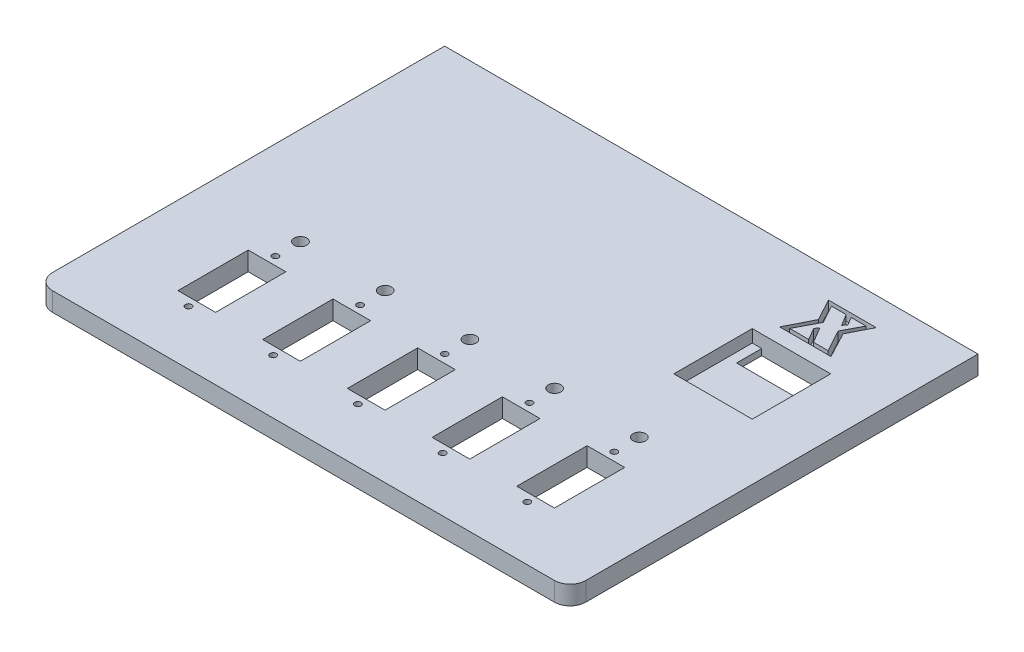
SolidWorks part; units mm, degrees
ref_plane "Front Plane" through (0, 0, 0) normal (0, 0, 1) x (1, 0, 0)
ref_plane "Top Plane" through (0, 0, 0) normal (0, 1, 0) x (1, 0, 0)
ref_plane "Right Plane" through (0, 0, 0) normal (1, 0, 0) x (0, 0, -1)
sketch "Sketch1" plane through (0, 0, 0) normal (0, 1, 0) x (1, 0, 0)
  line L1 (-85, -65) -> (85, -65)
  line L2 (-85, -65) -> (-85, 65)
  line L3 (-85, 65) -> (85, 65)
  line L4 (85, -65) -> (85, 65)
  line L5 (-85, -65) -> (85, 65) construction
  line L6 (-85, 65) -> (85, -65) construction
  point P0 (0, 0)
  dimension "D1" = 170
  dimension "D2" = 130
extrude "Boss-Extrude1" add sketch "Sketch1" along normal blind 6
sketch "Sketch2" plane through (0, 6, 0) normal (0, 1, 0) x (1, 0, 0)
  line L0 (-85, 65) -> (-85, -65) construction
  line L1 (-60, -45) -> (-48, -45)
  line L2 (-60, -45) -> (-60, -22.6)
  line L3 (-60, -22.6) -> (-48, -22.6)
  line L4 (-48, -45) -> (-48, -22.6)
  line L5 (-60, -45) -> (-48, -22.6) construction
  line L6 (-60, -22.6) -> (-48, -45) construction
  line L7 (-85, -65) -> (85, -65) construction
  circle A0 centre (-54, -19.95) radius 1
  circle A1 centre (-54, -47.65) radius 1
  circle A2 centre (-54, -11.95) radius 2
  point P0 (-54, -51.3962)
  point P14 (-54, -33.8)
  dimension "D5" = 2
  dimension "D6" = 2
  dimension "D12" = 4
  dimension "D13" = 8
  dimension "D14" = 6
  dimension "D15" = 6
  dimension "D1" = 12
  dimension "D2" = 22.4
  dimension "D3" = 25
  dimension "D4" = 20
  dimension "D7" = 27.7
  dimension "D8" = 2.65
  dimension "D9" = 2.65
  dimension "D10" = 13.85
  dimension "D11" = 13.85
extrude "Cut-Extrude1" cut sketch "Sketch2" against normal blind 10
pattern_linear "LPattern1" count 5 spacing 27 along (1, 0, 0) of "Cut-Extrude1"
sketch "Sketch8" plane through (0, 6, 0) normal (0, 1, 0) x (1, 0, 0)
  line L0 (85, 65) -> (-85, 65) construction
  line L1 (67, 11.05) -> (42, 11.05)
  line L2 (67, 11.05) -> (67, 36.05)
  line L3 (67, 36.05) -> (42, 36.05)
  line L4 (42, 11.05) -> (42, 36.05)
  line L6 (85, -65) -> (85, 65) construction
  dimension "D1" = 25
  dimension "D2" = 25
  dimension "D4" = 18
  dimension "D5" = 28.95
extrude "Cut-Extrude5" cut sketch "Sketch8" against normal through all
fillet "Fillet2" radius 5 2 edges at (-85, 3, 65) (85, 3, 65)
sketch "Sketch10" plane through (0, 0, 0) normal (0, -1, 0) x (1, 0, 0)
  line L0 (-80, 65) -> (80, 65) construction
  line L1 (-85, -65) -> (-85, 60) construction
  circle A0 centre (-73, 53) radius 9
  dimension "D1" = 18
  dimension "D3" = 12
  dimension "D2" = 12
extrude "Cut-Extrude6" cut sketch "Sketch10" against normal blind 2.6
mirror "Mirror1" about plane through (0, 0, 0) normal (1, 0, 0) of "Cut-Extrude6"
mirror "Mirror2" about plane through (0, 0, 0) normal (0, 0, 1) of "Mirror1"
sketch "Sketch11" plane through (0, 6, 0) normal (0, 1, 0) x (1, 0, 0)
  text T0 "<b>X</b>" font "G2 Geometr885 BT" height 15
  dimension "D1" = 3.7
extrude "Cut-Extrude7" cut sketch "Sketch11" against normal blind 3
sketch "Sketch13" plane through (0, 0, -11.05) normal (0, 0, -1) x (-1, 0, 0)
  line L1 (-42, 0) -> (-67, 0)
  line L2 (-42, 0) -> (-42, 2)
  line L3 (-42, 2) -> (-67, 2)
  line L4 (-67, 0) -> (-67, 2)
  dimension "D1" = 2
extrude "Boss-Extrude2" add sketch "Sketch13" along normal blind 17
sketch "Sketch14" plane through (0, 0, -36.05) normal (0, 0, 1) x (1, 0, 0)
  line L0 (-80, 0) -> (80, 0) construction
  line L1 (42, 0) -> (45, 0)
  line L2 (42, 0) -> (42, 2)
  line L3 (42, 2) -> (45, 2)
  line L4 (45, 0) -> (45, 2)
  line L5 (67, 0) -> (64, 0)
  line L6 (67, 0) -> (67, 2)
  line L7 (67, 2) -> (64, 2)
  line L8 (64, 0) -> (64, 2)
  line L9 (67, 0) -> (67, 6) construction
  dimension "D1" = 2
  dimension "D2" = 2
  dimension "D3" = 3
  dimension "D4" = 3
extrude "Boss-Extrude3" add sketch "Sketch14" along normal mid plane 20
